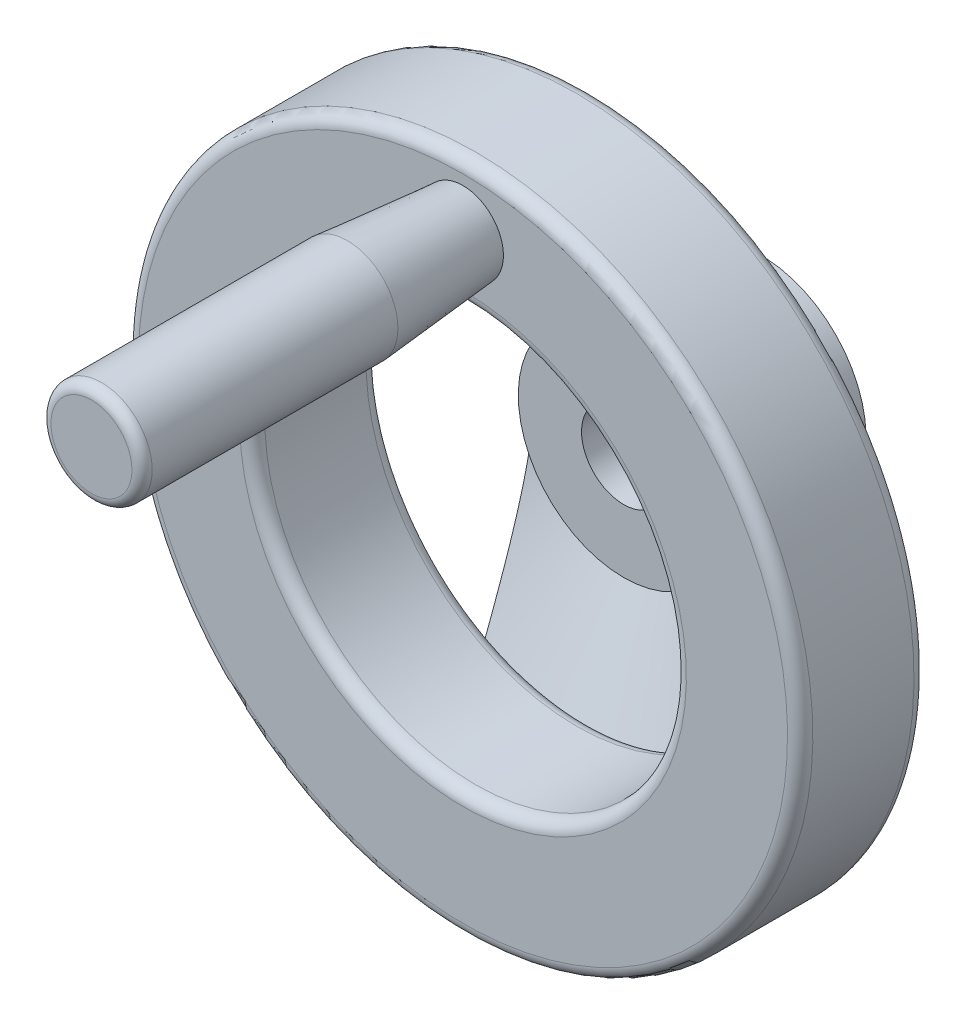
SolidWorks part; units mm, degrees
ref_plane "Front" through (0, 0, 0) normal (0, 0, 1) x (1, 0, 0)
ref_plane "Top" through (0, 0, 0) normal (0, 1, 0) x (1, 0, 0)
ref_plane "Right" through (0, 0, 0) normal (1, 0, 0) x (0, 0, -1)
sketch "Sketch1" plane through (0, 0, 0) normal (1, 0, 0) x (0, 0, -1)
  line L0 (0, 0) -> (-20.6375, 0) construction
  line L1 (0, -6.35) -> (-20.6375, -6.35)
  line L2 (-20.6375, -6.35) -> (-20.6375, -15.875)
  line L3 (-20.6375, -15.875) -> (-18.161, -15.875)
  line L4 (-18.161, -15.875) -> (-6.1913, -15.875)
  line L5 (-18.161, -15.875) -> (-25.7969, -33.655)
  line L6 (-25.7969, -33.655) -> (-25.7969, -36.5125)
  line L7 (-27.7019, -31.75) -> (-42.9419, -31.75)
  line L8 (-44.8469, -33.655) -> (-44.8469, -48.895)
  line L9 (-42.9419, -50.8) -> (-27.7019, -50.8)
  line L10 (-25.7969, -48.895) -> (-25.7969, -36.5125)
  line L11 (-25.7969, -36.5125) -> (-6.1913, -15.875)
  line L12 (-20.6375, 6.35) -> (0, 6.35) construction
  line L13 (-6.1913, -15.875) -> (0, -15.875)
  line L14 (0, -15.875) -> (0, -6.35)
  line L15 (0, -15.875) -> (0, 15.875) construction
  line L16 (-20.6375, -6.35) -> (-20.6375, 6.35) construction
  line L17 (0, -50.8) -> (0, 50.8) construction
  arc A0 (-25.7969, -33.655) -> (-27.7019, -31.75) centre (-27.7019, -33.655) ccw
  arc A1 (-42.9419, -31.75) -> (-44.8469, -33.655) centre (-42.9419, -33.655) ccw
  arc A2 (-44.8469, -48.895) -> (-42.9419, -50.8) centre (-42.9419, -48.895) ccw
  arc A3 (-27.7019, -50.8) -> (-25.7969, -48.895) centre (-27.7019, -48.895) ccw
  dimension "D2" = 2.4765
  dimension "D1" = 1.905
  dimension "C" = 31.75
  dimension "Hole Dia" = 12.7
  dimension "A" = 101.6
  dimension "B" = 44.8469
  dimension "D" = 20.6375
  dimension "Supplier G" = 19.05
  dimension "D3" = 6.1913
  dimension "D4" = 2.8575
revolve "Revolve1" add sketch "Sketch1" angle 360 about L0 region at (0, -41.275, 35.3219)
revolve "Revolve2" add sketch "Sketch1<3>" angle 360 region at (0, -11.1125, 10.3187) region at (0, -23.2352, 17.2468)
sketch "Sketch1<3>" plane through (0, 0, 0) normal (1, 0, 0) x (0, 0, -1) same geometry as "Sketch1"
sketch "Sketch2" plane through (0, 0, 0) normal (0, 0, 1) x (1, 0, 0)
  line L0 (-15.875, 48.2558) -> (-15.875, -48.2558)
  line L1 (15.875, 48.2558) -> (15.875, -48.2558)
  circle A2 centre (0, 0) radius 50.8 construction
  arc A3 (-15.875, 48.2558) -> (-15.875, -48.2558) centre (0, 0) ccw
  circle A6 centre (0, 0) radius 15.875 construction
  circle A7 centre (0, 0) radius 15.875 construction
  arc A8 (15.875, -48.2558) -> (15.875, 48.2558) centre (0, 0) ccw
extrude "Cut-Extrude1" cut sketch "Sketch2" along normal through all
sketch "Sketch4" plane through (0, 0, 0) normal (1, 0, 0) x (0, 0, -1)
  line L0 (-44.8469, 47.371) -> (-44.8469, 41.275)
  line L1 (-44.8469, 47.371) -> (-62.2663, 48.895)
  line L2 (-62.2663, 48.895) -> (-100.8063, 48.895)
  line L3 (-44.8469, 48.895) -> (-44.8469, -48.895) construction
  line L4 (-100.8063, 48.895) -> (-100.8063, 33.655) construction
  line L6 (-44.8469, 41.275) -> (-25.7969, 41.275) construction
  line L7 (-25.7969, -48.895) -> (-25.7969, 48.895) construction
  line L8 (0, 0) -> (-35.3219, 0) construction
  line L9 (-100.8063, 41.275) -> (-44.8469, 41.275)
  line L10 (-100.8063, 41.275) -> (-100.8063, 48.895)
  line L11 (-35.3219, -41.275) -> (-35.3219, 41.275) construction
  line L12 (-42.9419, 0) -> (-27.7019, 0) construction
  line L13 (-44.8469, -41.275) -> (-25.7969, -41.275) construction
  line L14 (-44.8469, -33.655) -> (-44.8469, -48.895) construction
  line L15 (-25.7969, -48.895) -> (-25.7969, -36.5125) construction
  dimension "D1" = 15.24
  dimension "D2" = 6.096
  dimension "D3" = 5
  dimension "E" = 55.9594
revolve "Revolve3" add sketch "Sketch4" angle 360 about L6
fillet "Fillet1" radius 1.524 1 edges at (7.62, 41.275, 100.8063)
equation "\"D1@Sketch1\" = \"Supplier G@Sketch1\" * .1"
equation "\"D2@Sketch1\" = \"D@Sketch1\" * .12"
equation "\"D3@Sketch1\" = \"D@Sketch1\" * .3"
equation "\"D4@Sketch1\" = \"Supplier G@Sketch1\" * .15"
equation "\"D1@Sketch4\" = \"C@Sketch1\" * .48"
equation "\"D2@Sketch4\" = \"D1@Sketch4\" * .4"
equation "\"D1@Fillet1\" = \"D1@Sketch4\" * .1"
